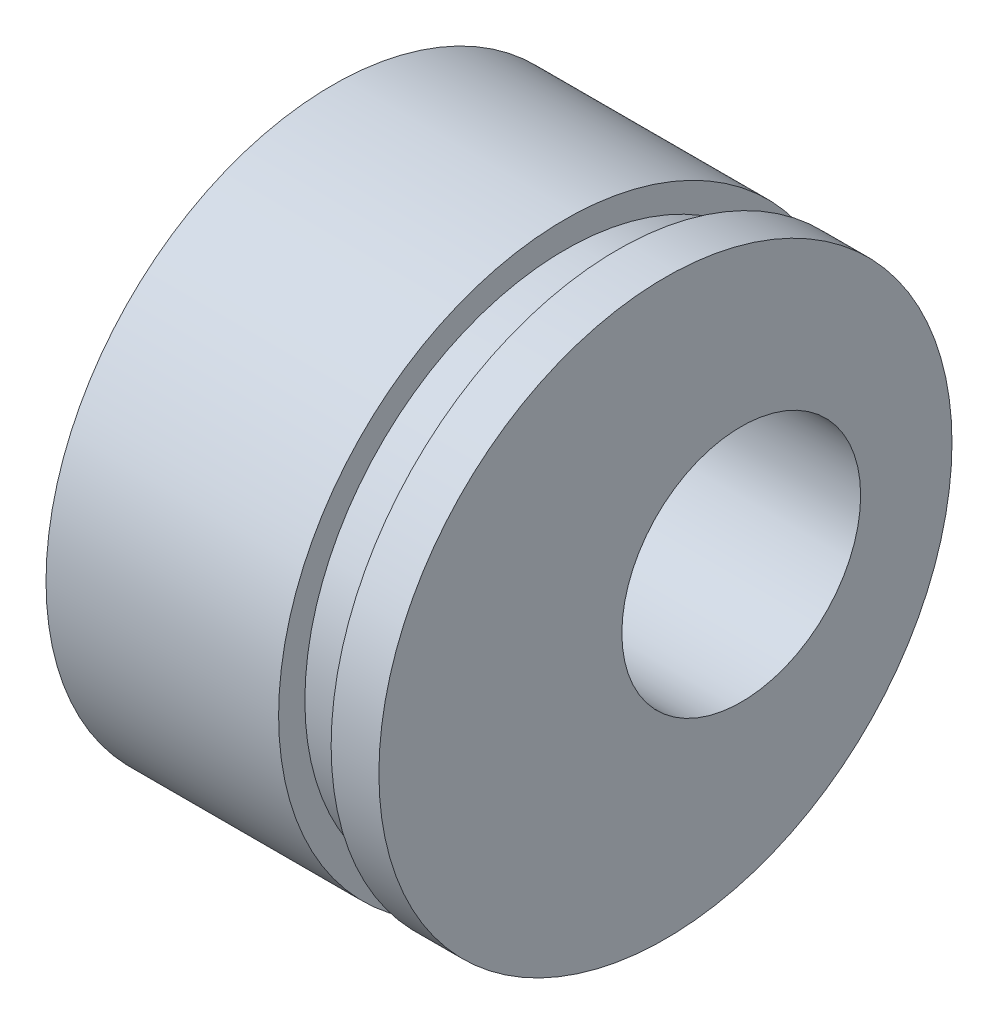
SolidWorks part; units mm, degrees
ref_plane "Front Plane" through (0, 0, 0) normal (0, 0, 1) x (1, 0, 0)
ref_plane "Top Plane" through (0, 0, 0) normal (0, 1, 0) x (1, 0, 0)
ref_plane "Right Plane" through (0, 0, 0) normal (1, 0, 0) x (0, 0, -1)
sketch "Sketch2" plane through (0, 0, 0) normal (0, 0, 1) x (1, 0, 0)
  line L0 (0, 0) -> (58.591, 0) construction
  line L2 (0, 0) -> (18.4, 0)
  line L3 (0, 0) -> (0, 2.5)
  line L4 (0, 2.5) -> (18.4, 2.5)
  line L5 (18.4, 0) -> (18.4, 2.5)
  line L6 (6.0094, 2.5) -> (6.0094, 6)
  line L11 (6.0094, 6) -> (9.9794, 6)
  line L16 (12.9794, 6) -> (12.9794, 3)
  line L17 (12.9794, 3) -> (13.6398, 3)
  line L18 (13.6398, 3) -> (13.6398, 2.5)
  line L19 (13.6398, 2.5) -> (6.0094, 2.5)
  line L22 (13.6398, 2.5) -> (16.1198, 2.5)
  line L23 (13.6398, 2.5) -> (13.6398, 4)
  line L24 (13.6398, 4) -> (16.1198, 4)
  line L25 (16.1198, 2.5) -> (16.1198, 4)
  line L27 (6.0094, 6) -> (9.9794, 6)
  line L28 (6.0094, 6) -> (6.0094, 9)
  line L29 (6.0094, 9) -> (9.9794, 9)
  line L30 (9.9794, 6) -> (9.9794, 9)
  line L31 (6.0094, 9) -> (6.0094, 8.25)
  line L32 (6.0094, 8.25) -> (5.0094, 8.25)
  line L33 (8.6609, 22.001) -> (8.6609, 12.476) construction
  line L34 (5.0094, 12.476) -> (12.3124, 12.476)
  line L35 (9.9794, 9) -> (12.3124, 9)
  line L36 (5.0094, 7.9375) -> (1.8344, 7.9375)
  line L37 (5.0094, 8.25) -> (5.0094, 12.476)
  line L38 (5.0094, 7.9375) -> (5.0094, 13.9365)
  line L39 (5.0094, 13.9365) -> (1.8344, 13.9365)
  line L40 (1.8344, 7.9375) -> (1.8344, 13.9365)
  line L41 (5.0094, 22.001) -> (12.3124, 22.001)
  line L42 (5.0094, 22.001) -> (5.0094, 30.1625)
  line L43 (5.0094, 30.1625) -> (12.3124, 30.1625)
  line L44 (12.3124, 22.001) -> (12.3124, 30.1625)
  line L49 (16.6398, 22.001) -> (16.6398, 7.5)
  line L51 (23.0198, 7.5) -> (23.0198, 6.5)
  line L54 (16.1198, 4) -> (13.6398, 4)
  line L56 (18.0398, 7.5) -> (23.0198, 7.5)
  line L57 (13.3124, 22.001) -> (16.6398, 22.001)
  line L58 (16.1198, 3.5) -> (20.0198, 3.5)
  line L59 (29.9098, 14) -> (26.9098, 11)
  line L60 (4.0094, 31.75) -> (18.0398, 31.75)
  line L61 (18.0398, 7.5) -> (23.0198, 7.5)
  line L62 (18.0398, 7.5) -> (18.0398, 12)
  line L63 (18.0398, 12) -> (23.0198, 12)
  line L64 (23.0198, 7.5) -> (23.0198, 12)
  line L65 (18.0398, 31.75) -> (18.0398, 12)
  line L66 (23.0198, 11) -> (26.9098, 11)
  line L67 (34.8098, 23) -> (31.3098, 19.5)
  line L68 (35.8098, 31) -> (38.7998, 33.99)
  line L69 (29.9098, 14) -> (29.9098, 15)
  line L70 (29.9098, 15) -> (22.9398, 15)
  line L71 (22.9398, 15) -> (21.0398, 15)
  line L72 (18.0398, 7.5) -> (16.6398, 7.5)
  line L73 (21.0398, 15) -> (21.0398, 43)
  line L74 (19.5798, 40) -> (9.6198, 40)
  line L75 (9.6198, 40) -> (4.0094, 40)
  line L76 (21.0398, 43) -> (19.5798, 43)
  line L77 (22.9398, 15) -> (29.9098, 15)
  line L78 (22.9398, 15) -> (22.9398, 21)
  line L79 (22.9398, 21) -> (29.9098, 21)
  line L80 (29.9098, 15) -> (29.9098, 21)
  line L81 (9.6198, 40) -> (19.5798, 40)
  line L82 (9.6198, 40) -> (9.6198, 50)
  line L83 (9.6198, 50) -> (19.5798, 50)
  line L84 (19.5798, 40) -> (19.5798, 50)
  line L85 (4.0094, 40) -> (4.0094, 31.75)
  line L86 (12.9794, 3) -> (12.9794, 2.5)
  line L87 (31.3098, 19.5) -> (29.9098, 19.5)
  line L88 (21.4694, 63.5) -> (21.4694, 51.308)
  line L89 (21.4694, 63.5) -> (25.9398, 63.5)
  line L90 (25.9398, 63.5) -> (25.9398, 25)
  line L91 (27.8398, 25) -> (25.9398, 25)
  line L92 (9.6198, 48) -> (8.1598, 48)
  line L93 (8.1598, 48) -> (8.1598, 53.476)
  line L94 (8.1598, 53.476) -> (19.5798, 53.476)
  line L95 (19.5798, 53.476) -> (19.5798, 50)
  line L96 (13.8698, 63.001) -> (13.8698, 53.476) construction
  line L97 (8.1598, 63.001) -> (19.5798, 63.001)
  line L98 (8.1598, 63.001) -> (8.1598, 68.2625)
  line L99 (8.1598, 68.2625) -> (19.5798, 68.2625)
  line L100 (19.5798, 63.001) -> (19.5798, 68.2625)
  line L101 (12.9794, 6) -> (11.9794, 6)
  line L102 (8.1598, 44.825) -> (4.9848, 44.825)
  line L103 (8.1598, 44.825) -> (8.1598, 54.9365)
  line L104 (8.1598, 54.9365) -> (4.9848, 54.9365)
  line L106 (9.9794, 6) -> (10.8794, 6)
  line L107 (27.8398, 25) -> (34.8098, 25)
  line L108 (34.8098, 25) -> (34.8098, 23)
  line L109 (0, 0) -> (-2, 0)
  line L110 (0, 0) -> (0, 11)
  line L111 (27.8398, 25) -> (34.8098, 25)
  line L112 (27.8398, 25) -> (27.8398, 32.5)
  line L113 (27.8398, 32.5) -> (34.8098, 32.5)
  line L114 (34.8098, 25) -> (34.8098, 32.5)
  line L115 (35.8098, 31) -> (34.8098, 31)
  line L116 (27.8398, 32.5) -> (27.8398, 64.5)
  line L117 (20.5373, 74.025) -> (6.2023, 74.025)
  line L118 (6.2023, 74.025) -> (6.2023, 76.2)
  line L119 (38.7998, 47.29) -> (30.8398, 55.25)
  line L120 (0, 11) -> (-2, 11)
  line L121 (38.7998, 43.815) -> (30.8623, 43.815)
  line L123 (-4.8152, 69.85) -> (1.5348, 76.2)
  line L124 (38.7998, 47.29) -> (38.7998, 33.99)
  line L125 (-2, 0) -> (-2, 11)
  line L126 (38.7998, 37.465) -> (30.8623, 37.465)
  line L127 (30.8623, 43.815) -> (30.8623, 37.465)
  line L128 (6.0094, 2.5) -> (6.0094, 0)
  line L129 (-0.0152, 63.5) -> (-0.0152, 30)
  line L132 (4.9848, 63.5) -> (-0.0152, 63.5)
  line L136 (-1.8152, 30) -> (-11.7752, 30)
  line L138 (-13.7752, 25.4) -> (-2, 25.4)
  line L139 (-2, 25.4) -> (-2, 11.5)
  line L140 (27.8398, 64.5) -> (20.5373, 64.5)
  line L141 (-1.8152, 30) -> (-11.7752, 30)
  line L142 (-1.8152, 30) -> (-1.8152, 39)
  line L143 (-1.8152, 39) -> (-11.7752, 39)
  line L144 (-11.7752, 30) -> (-11.7752, 39)
  line L145 (20.5373, 64.5) -> (20.5373, 74.025)
  line L146 (-12.7752, 37) -> (-12.7752, 47.29)
  line L147 (-12.7752, 37) -> (-11.7752, 37)
  line L148 (30.8398, 55.25) -> (30.8398, 76.2)
  line L149 (11.9794, 6) -> (11.9794, 5.45)
  line L154 (-2, 11.5) -> (0.5, 11.5)
  line L155 (4.9848, 60.6197) -> (24.0348, 60.6197)
  line L160 (4.9848, 60.6197) -> (4.9848, 55.8572)
  line L161 (4.9848, 55.8572) -> (24.0348, 55.8572)
  line L166 (24.0348, 60.6197) -> (24.0348, 55.8572)
  line L167 (4.9848, 60.6197) -> (24.0348, 55.8572) construction
  line L172 (4.9848, 55.8572) -> (24.0348, 60.6197) construction
  line L173 (24.0348, 62.2072) -> (25.9398, 62.2072)
  line L174 (11.9794, 5.45) -> (10.8794, 5.45)
  line L175 (10.8794, 6) -> (10.8794, 5.45)
  line L176 (24.0348, 62.2072) -> (24.0348, 54.2697)
  line L177 (24.0348, 54.2697) -> (25.9398, 54.2697)
  line L178 (25.9398, 62.2072) -> (25.9398, 54.2697)
  line L179 (24.0348, 62.2072) -> (25.9398, 54.2697) construction
  line L180 (24.0348, 54.2697) -> (25.9398, 62.2072) construction
  line L181 (3, 19.6197) -> (15.7, 19.6197)
  line L182 (3, 19.6197) -> (3, 14.8572)
  line L183 (3, 14.8572) -> (15.7, 14.8572)
  line L184 (15.7, 19.6197) -> (15.7, 14.8572)
  line L185 (3, 19.6197) -> (15.7, 14.8572) construction
  line L186 (3, 14.8572) -> (15.7, 19.6197) construction
  line L187 (15.7, 21.2072) -> (16.6398, 21.2072)
  line L188 (15.7, 21.2072) -> (15.7, 13.2697)
  line L189 (15.7, 13.2697) -> (16.6398, 13.2697)
  line L190 (16.6398, 21.2072) -> (16.6398, 13.2697)
  line L191 (15.7, 21.2072) -> (16.6398, 13.2697) construction
  line L192 (15.7, 13.2697) -> (16.6398, 21.2072) construction
  line L193 (0.5, 11.5) -> (0.5, 6.9375)
  line L194 (0.5, 6.9375) -> (1.8344, 6.9375)
  line L195 (23.0198, 6.5) -> (20.0198, 3.5)
  line L196 (4.9848, 63.5) -> (4.9848, 54.9365)
  line L197 (3, 43.825) -> (4.9848, 43.825)
  line L198 (1.8344, 6.9375) -> (1.8344, 7.9375)
  line L199 (6.0094, 0) -> (12.9794, 0)
  line L200 (12.9794, 0) -> (12.9794, 2.5)
  line L201 (18.0398, 31.75) -> (18.0398, 35.875)
  line L202 (18.0398, 35.875) -> (21.0398, 35.875)
  line L203 (30.8398, 76.2) -> (6.2023, 76.2)
  line L204 (2.7573, 69.85) -> (7.2023, 69.85) construction
  line L205 (7.2023, 67.4688) -> (26.2523, 67.4688)
  line L206 (7.2023, 74.025) -> (7.2023, 64.5)
  line L207 (7.2023, 64.5) -> (-1.8152, 64.5)
  line L208 (-1.8152, 64.5) -> (-1.8152, 39)
  line L209 (-12.7752, 47.29) -> (-4.8152, 55.25)
  line L210 (-4.8152, 55.25) -> (-4.8152, 69.85)
  line L211 (7.2023, 67.4688) -> (7.2023, 72.2312)
  line L212 (7.2023, 72.2312) -> (26.2523, 72.2313)
  line L213 (26.2523, 67.4688) -> (26.2523, 72.2313)
  line L214 (26.2523, 73.8187) -> (30.8398, 73.8187)
  line L215 (26.2523, 73.8187) -> (26.2523, 65.8813)
  line L216 (26.2523, 65.8813) -> (30.8398, 65.8813)
  line L217 (30.8398, 73.8187) -> (30.8398, 65.8813)
  line L218 (2.7573, 72.2313) -> (24.9823, 72.2313)
  line L219 (2.7573, 72.2313) -> (2.7573, 67.4687)
  line L220 (2.7573, 67.4687) -> (24.9823, 67.4687)
  line L221 (24.9823, 72.2313) -> (24.9823, 67.4687)
  line L222 (24.9823, 69.85) -> (20.5373, 69.85) construction
  line L223 (21.4694, 51.308) -> (22.9398, 51.308)
  line L224 (22.9398, 51.308) -> (22.9398, 21)
  line L225 (13.6398, 4) -> (13.6398, 12.2697)
  line L226 (13.6398, 12.2697) -> (13.3124, 12.2697)
  line L227 (13.3124, 12.2697) -> (13.3124, 22.001)
  line L228 (12.3124, 9) -> (12.3124, 12.476)
  line L229 (-1.8152, 30) -> (-0.0152, 30)
  line L230 (8.1598, 65.6317) -> (2.7573, 65.6317) construction
  line L231 (19.5798, 65.6317) -> (24.9823, 65.6317) construction
  line L232 (1.5348, 76.2) -> (6.2023, 76.2)
  line L233 (-11.7752, 30) -> (-13.7752, 30)
  line L234 (-13.7752, 30) -> (-13.7752, 25.4)
  line L235 (3, 13.9365) -> (3, 43.825)
  line L236 (4.9848, 54.9365) -> (4.9848, 44.825)
  line L237 (4.9848, 43.825) -> (4.9848, 44.825)
  circle A0 centre (26.8898, 25.95) radius 0.95
  circle A1 centre (21.9898, 15.95) radius 0.95
  circle A2 centre (17.3398, 8.2) radius 0.7
  circle A3 centre (10.4294, 6.45) radius 0.45
  circle A4 centre (-0.9152, 30.9) radius 0.9
  point P7 (24.9873, 58.2385)
  point P131 (16.1699, 17.2385)
  point P135 (14.5098, 58.2385)
  point P146 (9.35, 17.2385)
sketch "Sketch3" plane through (0, 0, 0) normal (0, 0, 1) x (1, 0, 0)
  line L0 (12.9794, 3) -> (12.9794, 2.5) construction
  line L1 (11.9794, 6) -> (11.9794, 5.45) construction
  line L2 (12.9794, 6) -> (11.9794, 6) construction
  line L3 (12.9794, 6) -> (12.9794, 3) construction
  line L5 (10.8794, 6) -> (10.8794, 5.45) construction
  line L6 (11.9794, 5.45) -> (10.8794, 5.45) construction
  line L7 (6.0094, 2.5) -> (6.0094, 6) construction
  line L8 (6.0094, 6) -> (9.9794, 6) construction
  line L9 (9.9794, 6) -> (10.8794, 6) construction
  line L10 (12.9794, 3) -> (12.9794, 2.5)
  line L11 (11.9794, 6) -> (11.9794, 5.45)
  line L12 (12.9794, 6) -> (11.9794, 6)
  line L13 (12.9794, 6) -> (12.9794, 3)
  line L15 (10.8794, 6) -> (10.8794, 5.45)
  line L16 (11.9794, 5.45) -> (10.8794, 5.45)
  line L17 (6.0094, 2.5) -> (6.0094, 6)
  line L18 (6.0094, 6) -> (9.9794, 6)
  line L19 (9.9794, 6) -> (10.8794, 6)
  line L20 (6.0094, 2.5) -> (6.0094, 0) construction
  line L21 (0, 0) -> (18.4, 0) construction
  line L22 (12.9794, 0) -> (12.9794, 2.5) construction
  line L23 (6.0094, 2.5) -> (6.0094, 0)
  line L24 (6.0094, 0) -> (12.9794, 0)
  line L25 (12.9794, 0) -> (12.9794, 2.5)
revolve "Revolve1" add sketch "Sketch3" angle 360 about L24
sketch "Sketch4" plane through (0, 0, 0) normal (1, 0, 0) x (0, 0, -1)
  line L0 (0, 0) -> (0, 69.85) construction
  line L1 (0, 0) -> (13.6271, 68.5079) construction
  line L2 (0, 0) -> (0, 58.2385) construction
  line L3 (0, 0) -> (50.436, 29.1192) construction
  line L4 (0, 0) -> (0, 31.75) construction
  line L5 (0, 0) -> (12.1502, 29.3332) construction
  line L6 (0, 0) -> (0, 17.2385) construction
  line L7 (0, 0) -> (14.929, 8.6192) construction
  line L8 (0, 0) -> (0, 58.2385) construction
  line L9 (0, 0) -> (50.436, 29.1192) construction
  line L10 (0, 0) -> (5.9583, 29.9542) construction
  line L11 (0, 0) -> (16.9677, 25.394) construction
  circle A0 centre (0, 0) radius 69.85 construction
  circle A1 centre (0, 0) radius 58.2385 construction
  circle A2 centre (0, 0) radius 31.75 construction
  circle A3 centre (0, 0) radius 17.2385 construction
  circle A4 centre (0, 69.85) radius 3.175
  circle A5 centre (0, 58.2385) radius 4.7625
  circle A6 centre (0, 31.75) radius 3.175
  circle A7 centre (0, 17.2385) radius 4.7625
  circle A8 centre (13.6271, 68.5079) radius 3.175
  circle A9 centre (26.7304, 64.533) radius 3.175
  circle A10 centre (38.8066, 58.0782) radius 3.175
  circle A11 centre (49.3914, 49.3914) radius 3.175
  circle A12 centre (58.0782, 38.8066) radius 3.175
  circle A13 centre (64.533, 26.7304) radius 3.175
  circle A14 centre (68.5079, 13.6271) radius 3.175
  circle A15 centre (69.85, 0) radius 3.175
  circle A16 centre (68.5079, -13.6271) radius 3.175
  circle A17 centre (64.533, -26.7304) radius 3.175
  circle A18 centre (58.0782, -38.8066) radius 3.175
  circle A19 centre (49.3914, -49.3914) radius 3.175
  circle A20 centre (38.8066, -58.0782) radius 3.175
  circle A21 centre (26.7304, -64.533) radius 3.175
  circle A22 centre (13.6271, -68.5079) radius 3.175
  circle A23 centre (0, -69.85) radius 3.175
  circle A24 centre (-13.6271, -68.5079) radius 3.175
  circle A25 centre (-26.7304, -64.533) radius 3.175
  circle A26 centre (-38.8066, -58.0782) radius 3.175
  circle A27 centre (-49.3914, -49.3914) radius 3.175
  circle A28 centre (-58.0782, -38.8066) radius 3.175
  circle A29 centre (-64.533, -26.7304) radius 3.175
  circle A30 centre (-68.5079, -13.6271) radius 3.175
  circle A31 centre (-69.85, 0) radius 3.175
  circle A32 centre (-68.5079, 13.6271) radius 3.175
  circle A33 centre (-64.533, 26.7304) radius 3.175
  circle A34 centre (-58.0782, 38.8066) radius 3.175
  circle A35 centre (-49.3914, 49.3914) radius 3.175
  circle A36 centre (-38.8066, 58.0782) radius 3.175
  circle A37 centre (-26.7304, 64.533) radius 3.175
  circle A38 centre (-13.6271, 68.5079) radius 3.175
  circle A47 centre (50.436, 29.1192) radius 4.7625
  circle A48 centre (50.436, -29.1192) radius 4.7625
  circle A49 centre (0, -58.2385) radius 4.7625
  circle A50 centre (-50.436, -29.1192) radius 4.7625
  circle A51 centre (-50.436, 29.1192) radius 4.7625
  circle A58 centre (12.1502, 29.3332) radius 3.175
  circle A59 centre (22.4506, 22.4506) radius 3.175
  circle A60 centre (29.3332, 12.1502) radius 3.175
  circle A61 centre (31.75, 0) radius 3.175
  circle A62 centre (29.3332, -12.1502) radius 3.175
  circle A63 centre (22.4506, -22.4506) radius 3.175
  circle A64 centre (12.1502, -29.3332) radius 3.175
  circle A65 centre (0, -31.75) radius 3.175
  circle A66 centre (-12.1502, -29.3332) radius 3.175
  circle A67 centre (-22.4506, -22.4506) radius 3.175
  circle A68 centre (-29.3332, -12.1502) radius 3.175
  circle A69 centre (-31.75, 0) radius 3.175
  circle A70 centre (-29.3332, 12.1502) radius 3.175
  circle A71 centre (-22.4506, 22.4506) radius 3.175
  circle A72 centre (14.929, 8.6192) radius 4.7625
  circle A73 centre (14.929, -8.6192) radius 4.7625
  circle A74 centre (0, -17.2385) radius 4.7625
  circle A75 centre (-14.929, -8.6192) radius 4.7625
  circle A76 centre (-14.929, 8.6192) radius 4.7625
  circle A77 centre (0, 0) radius 50
  circle A78 centre (0, 0) radius 9
  circle A79 centre (-12.1502, 29.3332) radius 3.175
  circle A80 centre (0, 0) radius 76.2
  circle A81 centre (0, 0) radius 74.025
  circle A82 centre (0, 69.85) radius 3.9687
  circle A83 centre (49.3914, 49.3914) radius 3.9687
  circle A84 centre (69.85, 0) radius 3.9688
  circle A85 centre (49.3914, -49.3914) radius 3.9687
  circle A86 centre (0, -69.85) radius 3.9687
  circle A87 centre (-49.3914, -49.3914) radius 3.9687
  circle A88 centre (-69.85, 0) radius 3.9688
  circle A89 centre (-49.3914, 49.3914) radius 3.9687
  circle A90 centre (0, 69.85) radius 2.3812
  circle A91 centre (13.6271, 68.5079) radius 2.3812
  circle A92 centre (26.7304, 64.533) radius 2.3813
  circle A93 centre (38.8066, 58.0782) radius 2.3812
  circle A94 centre (49.3914, 49.3914) radius 2.3812
  circle A95 centre (58.0782, 38.8066) radius 2.3812
  circle A96 centre (64.533, 26.7304) radius 2.3813
  circle A97 centre (68.5079, 13.6271) radius 2.3813
  circle A98 centre (69.85, 0) radius 2.3813
  circle A99 centre (68.5079, -13.6271) radius 2.3813
  circle A100 centre (64.533, -26.7304) radius 2.3813
  circle A101 centre (58.0782, -38.8066) radius 2.3812
  circle A102 centre (49.3914, -49.3914) radius 2.3812
  circle A103 centre (38.8066, -58.0782) radius 2.3812
  circle A104 centre (26.7304, -64.533) radius 2.3813
  circle A105 centre (13.6271, -68.5079) radius 2.3812
  circle A106 centre (0, -69.85) radius 2.3812
  circle A107 centre (-13.6271, -68.5079) radius 2.3812
  circle A108 centre (-26.7304, -64.533) radius 2.3813
  circle A109 centre (-38.8066, -58.0782) radius 2.3812
  circle A110 centre (-49.3914, -49.3914) radius 2.3812
  circle A111 centre (-58.0782, -38.8066) radius 2.3812
  circle A112 centre (-64.533, -26.7304) radius 2.3812
  arc A113 (3.0399, 30.8338) -> (8.9911, 29.65) centre (5.9583, 29.9542) cw
  arc A114 (14.6081, 27.3234) -> (19.6532, 23.9523) centre (16.9677, 25.394) cw
  arc A115 (23.9523, 19.6532) -> (27.3234, 14.6081) centre (25.394, 16.9677) cw
  arc A116 (29.65, 8.9911) -> (30.8338, 3.0399) centre (29.9542, 5.9583) cw
  arc A117 (30.8338, -3.0399) -> (29.65, -8.9911) centre (29.9542, -5.9583) cw
  arc A118 (27.3234, -14.6081) -> (23.9523, -19.6532) centre (25.394, -16.9677) cw
  arc A119 (19.6532, -23.9523) -> (14.6081, -27.3234) centre (16.9677, -25.394) cw
  arc A120 (8.9911, -29.65) -> (3.0399, -30.8338) centre (5.9583, -29.9542) cw
  arc A121 (-3.0399, -30.8338) -> (-8.9911, -29.65) centre (-5.9583, -29.9542) cw
  arc A122 (-14.6081, -27.3234) -> (-19.6532, -23.9523) centre (-16.9677, -25.394) cw
  arc A123 (-23.9523, -19.6532) -> (-27.3234, -14.6081) centre (-25.394, -16.9677) cw
  arc A124 (-29.65, -8.9911) -> (-30.8338, -3.0399) centre (-29.9542, -5.9583) cw
  arc A125 (-30.8338, 3.0399) -> (-29.65, 8.9911) centre (-29.9542, 5.9583) cw
  arc A126 (-27.3234, 14.6081) -> (-23.9523, 19.6532) centre (-25.394, 16.9677) cw
  arc A127 (-19.6532, 23.9523) -> (-14.6081, 27.3234) centre (-16.9677, 25.394) cw
  arc A128 (-8.9911, 29.65) -> (-3.0399, 30.8338) centre (-5.9583, 29.9542) cw
  arc A129 (26.9875, 0) -> (26.9932, 0.1932) centre (30.2705, 0) cw
  arc A130 (65.0988, 0.2771) -> (65.0875, 0) centre (68.4964, 0) ccw
  circle A131 centre (1.5875, 0) radius 40
  circle A132 centre (1.5875, 0) radius 2.5
  circle A133 centre (1.5875, 0) radius 3
  circle A134 centre (1.5875, 0) radius 43
  circle A135 centre (-68.5079, -13.6271) radius 2.3813
  circle A136 centre (-69.85, 0) radius 2.3813
  circle A137 centre (-68.5079, 13.6271) radius 2.3813
  circle A138 centre (-64.533, 26.7304) radius 2.3812
  circle A139 centre (-58.0782, 38.8066) radius 2.3812
  circle A140 centre (-49.3914, 49.3914) radius 2.3812
  circle A141 centre (-38.8066, 58.0782) radius 2.3812
  circle A142 centre (-26.7304, 64.533) radius 2.3813
  circle A143 centre (-13.6271, 68.5079) radius 2.3812
  circle A144 centre (0, 58.2385) radius 2.3812
  circle A145 centre (0, 58.2385) radius 3.9688
  circle A146 centre (50.436, 29.1192) radius 3.9688
  circle A147 centre (50.436, 29.1192) radius 2.3813
  circle A148 centre (50.436, -29.1192) radius 3.9687
  circle A149 centre (50.436, -29.1192) radius 2.3812
  circle A150 centre (0, -58.2385) radius 3.9687
  circle A151 centre (0, -58.2385) radius 2.3812
  circle A152 centre (-50.436, -29.1192) radius 3.9687
  circle A153 centre (-50.436, -29.1192) radius 2.3812
  circle A154 centre (-50.436, 29.1192) radius 3.9687
  circle A155 centre (-50.436, 29.1192) radius 2.3812
  spline S1 degree 4 poles (26.9875, 0) (26.9875, -0.0248) (26.9882, -0.0743) (26.9912, -0.1613) (26.9992, -0.2849) (27.0142, -0.4323) (27.0403, -0.5994) (27.0821, -0.7965) (27.1455, -1.0177) (27.2241, -1.2336) (27.3173, -1.4437) (27.4329, -1.6623) (27.5739, -1.8864) (27.7427, -2.1125) (27.9417, -2.3365) (28.1305, -2.5184) (28.3007, -2.6647) (28.4457, -2.7828) (28.5617, -2.8775) (28.6745, -2.9758) (28.7813, -3.0807) (28.9057, -3.2206) (29.0482, -3.4108) (29.197, -3.6576) (29.3758, -4.0447) (29.5291, -4.5502) (29.6152, -5.1612) (29.5933, -5.8758) (29.4507, -6.5869) (29.186, -7.2733) (28.8461, -7.831) (28.4818, -8.2549) (28.1375, -8.5536) (27.8792, -8.7284) (27.6484, -8.8496) (27.4154, -8.9438) (27.2144, -9.0029) (27.0118, -9.0554) (26.7709, -9.1263) (26.5334, -9.2082) (26.2634, -9.3231) (25.9685, -9.4827) (25.5538, -9.7623) (25.0678, -10.2216) (24.6281, -10.8948) (24.3613, -11.7878) (24.3459, -12.6097) (24.4764, -13.2366) (24.6525, -13.7006) (24.8058, -14.0202) (24.9382, -14.271) (25.0503, -14.5321) (25.1258, -14.8064) (25.1736, -15.0995) (25.1911, -15.4094) (25.1742, -15.8163) (25.0891, -16.3148) (24.907, -16.8764) (24.5182, -17.6315) (23.9757, -18.2942) (23.3695, -18.7764) (22.7564, -19.084) (22.3641, -19.2199) (22.0554, -19.2923) (21.7533, -19.3289) (21.4612, -19.3296) (21.1723, -19.2896) (20.8852, -19.2417) (20.5956, -19.2104) (20.3043, -19.1994) (19.8669, -19.2177) (19.2899, -19.3231) (18.5833, -19.6092) (17.8444, -20.1834) (17.3807, -20.828) (17.1316, -21.424) (17.0182, -21.8879) (16.9714, -22.1971) (16.9537, -22.4701) (16.9533, -22.7044) (16.9619, -22.9384) (16.9737, -23.1333) (16.977, -23.3286) (16.9594, -23.5624) (16.9177, -23.8101) (16.834, -24.1055) (16.6578, -24.5276) (16.3623, -25.0151) (15.9278, -25.5198) (15.3432, -25.99) (14.6957, -26.3472) (14.0068, -26.5857) (13.3856, -26.6851) (12.847, -26.6849) (12.4166, -26.6224) (12.1324, -26.5468) (11.9058, -26.4598) (11.7342, -26.3753) (11.6017, -26.2989) (11.4727, -26.2169) (11.3444, -26.1337) (11.1825, -26.0322) (10.9836, -25.9179) (10.7435, -25.7991) (10.4587, -25.6867) (10.0106, -25.5536) (9.3843, -25.468) (8.599, -25.5363) (7.7243, -25.8773) (7.1093, -26.3459) (6.716, -26.8042) (6.4745, -27.1841) (6.3352, -27.4489) (6.215, -27.7227) (6.1113, -28.0028) (5.9959, -28.2789) (5.841, -28.5357) (5.6522, -28.7792) (5.4316, -29.007) (5.1188, -29.2711) (4.6965, -29.5439) (4.1624, -29.7882) (3.5487, -29.9564) (2.9521, -30.0296) (2.386, -30.0225) (1.8595, -29.949) (1.3409, -29.8055) (0.9058, -29.6147) (0.5544, -29.4004) (0.2828, -29.1832) (0.0847, -28.9875) (-0.0865, -28.768) (-0.2353, -28.5332) (-0.3904, -28.3016) (-0.5598, -28.0786) (-0.792, -27.8146) (-1.1036, -27.5274) (-1.5105, -27.2448) (-2.0688, -26.9834) (-2.7167, -26.8202) (-3.459, -26.7949) (-4.1529, -26.9407) (-4.7224, -27.1899) (-5.1296, -27.455) (-5.3866, -27.661) (-5.5925, -27.8507) (-5.7558, -28.014) (-5.9199, -28.1766) (-6.0977, -28.3246) (-6.3382, -28.4851) (-6.6906, -28.6628) (-7.1669, -28.8182) (-7.7668, -28.9076) (-8.4201, -28.8957) (-9.0747, -28.7804) (-9.7144, -28.5614) (-10.3217, -28.2381) (-10.8061, -27.8636) (-11.1671, -27.4837) (-11.4143, -27.1402) (-11.5734, -26.859) (-11.6946, -26.573) (-11.7735, -26.2857) (-11.8173, -25.9915) (-11.8668, -25.6988) (-11.9353, -25.4093) (-12.0257, -25.1261) (-12.198, -24.7091) (-12.5089, -24.187) (-13.0379, -23.6191) (-13.8448, -23.1355) (-14.6072, -22.9365) (-15.2369, -22.9149) (-15.701, -22.9694) (-16.0024, -23.0316) (-16.2609, -23.107) (-16.4782, -23.1841) (-16.6576, -23.2529) (-16.8015, -23.307) (-16.9839, -23.3672) (-17.2087, -23.4203) (-17.4853, -23.4534) (-17.811, -23.4543) (-18.2291, -23.4104) (-18.7305, -23.2885) (-19.2884, -23.06) (-19.8603, -22.7052) (-20.3581, -22.2764) (-20.7758, -21.7899) (-21.1086, -21.2598) (-21.3336, -20.7318) (-21.4619, -20.2263) (-21.5006, -19.8113) (-21.4889, -19.4989) (-21.4468, -19.2424) (-21.3965, -19.0408) (-21.34, -18.8332) (-21.2878, -18.6168) (-21.2341, -18.3322) (-21.1962, -17.9773) (-21.1985, -17.5604) (-21.2781, -17.0173) (-21.4721, -16.4256) (-21.838, -15.7861) (-22.3482, -15.2578) (-22.8946, -14.8957) (-23.3828, -14.6878) (-23.7368, -14.5834) (-24.0536, -14.5215) (-24.3285, -14.4876) (-24.6045, -14.47) (-24.8811, -14.458) (-25.1556, -14.4184) (-25.4228, -14.3439) (-25.6932, -14.2375) (-26.1109, -14.0218) (-26.5677, -13.6822) (-27.0258, -13.1981) (-27.4314, -12.5682) (-27.7017, -11.9578) (-27.8746, -11.3112) (-27.9332, -10.727) (-27.9111, -10.2247) (-27.8415, -9.8214) (-27.7568, -9.5159) (-27.6427, -9.2298) (-27.5004, -8.9659) (-27.3212, -8.7261) (-27.1301, -8.4966) (-26.9071, -8.1967) (-26.6417, -7.7583) (-26.3997, -7.1508) (-26.2841, -6.3875) (-26.3642, -5.5798) (-26.6019, -4.9055) (-26.9193, -4.3761) (-27.2736, -3.9636) (-27.583, -3.6904) (-27.8719, -3.4871) (-28.1186, -3.3407) (-28.3135, -3.2371) (-28.5043, -3.1411) (-28.6854, -3.0419) (-28.9002, -2.8984) (-29.1355, -2.6958) (-29.4123, -2.3882) (-29.6958, -1.9552) (-29.932, -1.437) (-30.0985, -0.839) (-30.1779, -0.2025) (-30.1603, 0.4599) (-30.0348, 1.1323) (-29.8199, 1.711) (-29.5617, 2.1719) (-29.3035, 2.5118) (-29.0784, 2.748) (-28.8655, 2.924) (-28.6761, 3.0468) (-28.5112, 3.1367) (-28.3775, 3.205) (-28.2106, 3.2911) (-28.0136, 3.4005) (-27.7912, 3.5413) (-27.5508, 3.7219) (-27.2011, 4.0343) (-26.7941, 4.5285) (-26.4419, 5.234) (-26.2777, 6.1494) (-26.351, 6.9081) (-26.5268, 7.4739) (-26.7218, 7.8823) (-26.8619, 8.1196) (-26.9953, 8.3144) (-27.1373, 8.5028) (-27.2613, 8.6553) (-27.3845, 8.8088) (-27.518, 9.0035) (-27.6324, 9.2103) (-27.7412, 9.4693) (-27.8326, 9.7814) (-27.9074, 10.1885) (-27.9345, 10.6913) (-27.8808, 11.2771) (-27.6878, 12.0229) (-27.3166, 12.8111) (-26.8405, 13.4278) (-26.3243, 13.8718) (-25.9118, 14.1263) (-25.6503, 14.2566) (-25.3769, 14.3596) (-25.0933, 14.4318) (-24.8027, 14.4634) (-24.5112, 14.4738) (-24.1629, 14.5033) (-23.7608, 14.5717) (-23.1887, 14.7443) (-22.5511, 15.0901) (-21.962, 15.6231) (-21.544, 16.2749) (-21.3217, 16.857) (-21.2175, 17.3851) (-21.1902, 17.8397) (-21.2185, 18.2374) (-21.2771, 18.5739) (-21.3443, 18.8506) (-21.405, 19.0706) (-21.4579, 19.2928) (-21.4883, 19.5194) (-21.4981, 19.805) (-21.4664, 20.1907) (-21.3565, 20.6672) (-21.1331, 21.2135) (-20.8025, 21.7541) (-20.3882, 22.2461) (-19.8974, 22.677) (-19.3379, 23.033) (-18.7964, 23.2649) (-18.309, 23.3941) (-17.8981, 23.4483) (-17.5726, 23.4572) (-17.2924, 23.4331) (-17.0602, 23.3874) (-16.8337, 23.3199) (-16.6495, 23.2499) (-16.4659, 23.1791) (-16.2424, 23.1025) (-16.0156, 23.0362) (-15.7461, 22.9768) (-15.2967, 22.9185) (-14.7035, 22.9278) (-13.9592, 23.0948) (-13.1407, 23.5365) (-12.5805, 24.0908) (-12.2382, 24.6309) (-12.0505, 25.0599) (-11.9538, 25.3442) (-11.8892, 25.5989) (-11.8463, 25.8198) (-11.8162, 26.0048) (-11.7926, 26.153) (-11.7577, 26.3372) (-11.6989, 26.5548) (-11.5969, 26.8111) (-11.4414, 27.0975) (-11.1977, 27.4473) (-10.8392, 27.8343) (-10.3554, 28.2166) (-9.7549, 28.5431) (-9.1303, 28.7642) (-8.5, 28.8851) (-7.879, 28.911) (-7.3126, 28.8458) (-6.8128, 28.7091) (-6.4345, 28.54) (-6.1692, 28.378) (-5.9665, 28.2173) (-5.8163, 28.0752) (-5.6659, 27.9232) (-5.5067, 27.7699) (-5.2907, 27.5806) (-5.0072, 27.369) (-4.6509, 27.1597) (-4.148, 26.9513) (-3.5452, 26.8146) (-2.8302, 26.7991) (-2.0381, 26.9749) (-1.3495, 27.3225) (-0.8483, 27.741) (-0.5146, 28.1291) (-0.2991, 28.4338) (-0.1401, 28.6862) (0.0331, 28.93) (0.2405, 29.146) (0.4774, 29.3422) (0.7418, 29.5165) (1.1036, 29.7066) (1.5741, 29.882) (2.1471, 30.006) (2.8151, 30.041) (3.4791, 29.9721) (4.2039, 29.7804) (4.8064, 29.4933) (5.2708, 29.1628) (5.6049, 28.8311) (5.7894, 28.6062) (5.9424, 28.3744) (6.0642, 28.1249) (6.161, 27.8653) (6.2635, 27.608) (6.3813, 27.357) (6.5388, 27.0748) (6.7484, 26.7704) (7.0986, 26.3707) (7.6135, 25.9641) (8.2747, 25.644) (8.9962, 25.4959) (9.6181, 25.496) (10.1582, 25.5894) (10.5546, 25.7168) (10.8796, 25.8629) (11.1331, 26.0022) (11.3224, 26.1188) (11.5021, 26.2366) (11.6784, 26.3463) (11.9094, 26.4649) (12.2028, 26.5718) (12.6092, 26.6624) (13.1291, 26.6958) (13.7, 26.6444) (14.3062, 26.4914) (14.8974, 26.2443) (15.459, 25.9029) (15.9732, 25.4681) (16.3631, 25.0071) (16.6337, 24.567) (16.8044, 24.1822) (16.9036, 23.8716) (16.9571, 23.5978) (16.9755, 23.3672) (16.9741, 23.1748) (16.9669, 23.0211) (16.9571, 22.8289) (16.9512, 22.5982) (16.9599, 22.3287) (16.9946, 22.0224) (17.0874, 21.5638) (17.3043, 20.9714) (17.7315, 20.3087) (18.4426, 19.693) (19.1468, 19.3677) (19.739, 19.2351) (20.1882, 19.2012) (20.4852, 19.2034) (20.7812, 19.2282) (21.0745, 19.2719) (21.3675, 19.3208) (21.6648, 19.3336) (21.9737, 19.306) (22.2899, 19.241) (22.6922, 19.1116) (23.1641, 18.8854) (23.669, 18.5404) (24.1634, 18.0628) (24.569, 17.5219) (24.8807, 16.9345) (25.0937, 16.316) (25.184, 15.7743) (25.1924, 15.3317) (25.1581, 14.9969) (25.1154, 14.7695) (25.0522, 14.5468) (24.9658, 14.3321) (24.8616, 14.1257) (24.7568, 13.9198) (24.6402, 13.6649) (24.524, 13.3562) (24.3985, 12.886) (24.3389, 12.2663) (24.4166, 11.5605) (24.6979, 10.7931) (25.0952, 10.2042) (25.5426, 9.7706) (25.9551, 9.4883) (26.2689, 9.3208) (26.5627, 9.1971) (26.83, 9.1062) (27.1019, 9.0315) (27.3749, 8.9598) (27.6385, 8.8574) (27.887, 8.7225) (28.1969, 8.5098) (28.5449, 8.1936) (28.9002, 7.7549) (29.2229, 7.1817) (29.4529, 6.562) (29.5858, 5.9108) (29.6165, 5.2432) (29.5485, 4.659) (29.4188, 4.1725) (29.2636, 3.7931) (29.1144, 3.5129) (28.9404, 3.2582) (28.7432, 3.0317) (28.5155, 2.8371) (28.281, 2.6515) (28.0578, 2.4519) (27.8492, 2.2371) (27.6347, 1.9761) (27.4574, 1.7102) (27.3152, 1.4444) (27.2047, 1.1845) (27.1307, 0.9703) (27.0789, 0.7793) (27.0441, 0.6164) (27.021, 0.472) (27.0061, 0.351) (26.9981, 0.2662) (26.9946, 0.2176) (26.9932, 0.1932) knots 0.06864 0.06864 0.06864 0.06864 0.06864 0.069106 0.069571 0.070037 0.070502 0.071433 0.072364 0.073295 0.074226 0.075157 0.076088 0.077301 0.078514 0.079727 0.08094 0.081547 0.082153 0.08276 0.083366 0.083973 0.084579 0.085792 0.087214 0.088636 0.091479 0.094323 0.097166 0.100174 0.103182 0.10619 0.107694 0.109198 0.110555 0.111234 0.111912 0.113269 0.113948 0.114626 0.115983 0.11734 0.118697 0.120055 0.12408 0.128106 0.131537 0.134967 0.137266 0.138415 0.139565 0.140714 0.141863 0.143013 0.144162 0.145524 0.146885 0.149608 0.152331 0.155054 0.160594 0.163364 0.164749 0.166134 0.167314 0.168495 0.169675 0.170855 0.172035 0.173215 0.174395 0.175575 0.179125 0.182676 0.186612 0.190548 0.191813 0.193079 0.194345 0.195611 0.196244 0.196877 0.198142 0.198775 0.199408 0.200674 0.202207 0.203741 0.206808 0.209874 0.212941 0.21584 0.218738 0.221637 0.223086 0.224535 0.225775 0.226394 0.227014 0.227634 0.228253 0.228873 0.229493 0.230732 0.231971 0.233211 0.23445 0.238303 0.242155 0.245814 0.249472 0.250683 0.251894 0.253105 0.254316 0.255527 0.256738 0.257949 0.25916 0.260514 0.261868 0.264577 0.267285 0.269993 0.272142 0.27429 0.276439 0.278588 0.280839 0.281965 0.283091 0.284217 0.285343 0.286469 0.287595 0.288737 0.289879 0.292163 0.294447 0.296732 0.299827 0.302922 0.306383 0.308113 0.309844 0.31078 0.311716 0.312652 0.313588 0.314524 0.31546 0.317332 0.319969 0.322606 0.325244 0.327881 0.330703 0.333524 0.336346 0.337757 0.339168 0.340372 0.341576 0.34278 0.343984 0.345188 0.346392 0.347596 0.3488 0.352495 0.356189 0.36002 0.36385 0.365096 0.366342 0.367588 0.368834 0.369457 0.370079 0.370702 0.371325 0.372571 0.373817 0.375207 0.376596 0.379375 0.382154 0.384933 0.387459 0.389986 0.392513 0.39504 0.396723 0.398407 0.399249 0.400091 0.400932 0.401774 0.402737 0.4037 0.405625 0.407551 0.409476 0.412569 0.415662 0.41939 0.421254 0.423119 0.42424 0.425361 0.426483 0.427604 0.428726 0.429847 0.430969 0.43209 0.433431 0.437455 0.440138 0.44282 0.445528 0.448236 0.450943 0.452297 0.453651 0.454862 0.456073 0.457284 0.458495 0.459706 0.460916 0.463338 0.466783 0.470228 0.473297 0.476366 0.478273 0.480179 0.482085 0.483038 0.483991 0.484828 0.485664 0.486501 0.487337 0.48901 0.490683 0.493189 0.495695 0.498202 0.500708 0.503552 0.506397 0.509241 0.510663 0.512085 0.513303 0.514521 0.51513 0.515738 0.516347 0.516956 0.518174 0.519391 0.520609 0.521827 0.525766 0.529706 0.533208 0.53671 0.537985 0.53926 0.540535 0.541173 0.54181 0.543085 0.543723 0.54436 0.545635 0.54691 0.548267 0.549623 0.552335 0.555047 0.55776 0.562061 0.566363 0.567545 0.568728 0.56991 0.571092 0.572275 0.573457 0.574639 0.575822 0.577939 0.580057 0.584292 0.587472 0.590653 0.592493 0.594334 0.596174 0.598014 0.59894 0.599865 0.60079 0.601715 0.60264 0.603565 0.605415 0.607973 0.610531 0.61309 0.615648 0.618364 0.62108 0.623796 0.625154 0.626512 0.627788 0.629065 0.629703 0.630341 0.631618 0.632256 0.632895 0.634171 0.635448 0.636724 0.640232 0.643739 0.647674 0.651609 0.652825 0.65404 0.655256 0.656472 0.65708 0.657688 0.658296 0.658904 0.66012 0.661336 0.662756 0.664177 0.667018 0.669858 0.672699 0.675209 0.677718 0.680227 0.682736 0.684412 0.686087 0.686924 0.687762 0.688599 0.689437 0.690391 0.691345 0.693254 0.695162 0.697071 0.700143 0.703216 0.706655 0.710095 0.712514 0.713723 0.714933 0.716142 0.717352 0.718561 0.719771 0.721123 0.722475 0.725179 0.727883 0.730587 0.733273 0.735959 0.739989 0.741332 0.742455 0.743577 0.7447 0.745823 0.746945 0.748068 0.749191 0.750314 0.752181 0.754048 0.757782 0.760871 0.763961 0.765883 0.767806 0.769729 0.77069 0.771651 0.772492 0.773333 0.774174 0.775015 0.776698 0.77838 0.780903 0.783427 0.785951 0.788475 0.791257 0.794039 0.796822 0.798213 0.799604 0.800852 0.802099 0.802723 0.803347 0.803971 0.804595 0.805842 0.80709 0.808337 0.809585 0.81342 0.817255 0.820945 0.824634 0.825837 0.827039 0.828242 0.829444 0.830647 0.831849 0.833052 0.834254 0.835663 0.837072 0.83989 0.842708 0.845526 0.848167 0.850807 0.853447 0.856087 0.857024 0.857961 0.858897 0.859834 0.860771 0.861707 0.862644 0.863581 0.865314 0.867048 0.870515 0.873613 0.876711 0.880181 0.881916 0.883651 0.884794 0.885937 0.887081 0.888224 0.889367 0.89051 0.891653 0.892797 0.895451 0.898105 0.90076 0.903414 0.906126 0.908838 0.911549 0.912905 0.914261 0.915474 0.916686 0.917899 0.919111 0.920323 0.921536 0.922748 0.923961 0.925793 0.926709 0.927625 0.928541 0.929457 0.929915 0.930373 0.930831 0.931289 0.931289 0.931289 0.931289 0.931289
  spline S3 degree 4 poles (65.0875, 0) (65.0875, -0.2085) (65.1336, -0.6093) (65.3196, -1.4523) (65.739, -2.0447) (66.242, -2.6341) (66.7299, -3.0916) (67.1731, -3.6257) (67.5219, -4.2566) (67.8399, -5.1354) (68.0042, -6.2629) (67.9043, -7.3956) (67.5534, -8.464) (67.1166, -9.2437) (66.7001, -9.7852) (66.2223, -10.2316) (65.7042, -10.5824) (65.1033, -10.9671) (64.5015, -11.4984) (63.9836, -12.2541) (63.7076, -13.0981) (63.6577, -13.8665) (63.7509, -14.5541) (63.9279, -15.1344) (64.2231, -15.7099) (64.6171, -16.2749) (64.9859, -16.8848) (65.2405, -17.5795) (65.3772, -18.3315) (65.3953, -19.1188) (65.2888, -19.9454) (65.0416, -20.7887) (64.6379, -21.6235) (64.0595, -22.4019) (63.3699, -23.0372) (62.5888, -23.4701) (61.782, -23.7464) (61.0578, -24.1183) (60.3658, -24.7064) (59.8816, -25.4078) (59.6093, -26.1527) (59.5127, -26.9191) (59.5498, -27.5888) (59.7273, -28.2781) (60.0289, -28.9687) (60.2831, -29.7025) (60.3758, -30.5026) (60.3272, -31.328) (60.135, -32.1571) (59.8183, -32.9321) (59.3945, -33.6382) (58.8781, -34.2627) (58.2824, -34.7917) (57.6299, -35.2075) (56.9378, -35.4918) (56.2305, -35.6333) (55.5425, -35.7436) (54.9192, -35.9451) (54.3784, -36.2357) (53.8226, -36.6647) (53.3379, -37.2279) (52.9635, -37.9633) (52.7754, -38.8477) (52.8002, -39.6949) (52.9662, -40.4335) (53.0501, -41.0953) (53.0299, -41.6741) (52.9556, -42.1601) (52.7999, -42.7542) (52.5204, -43.4371) (52.0123, -44.2743) (51.2999, -45.0323) (50.5074, -45.5996) (49.6888, -45.9749) (49.0001, -46.1726) (48.294, -46.2386) (47.5903, -46.2021) (46.9326, -46.2102) (46.3301, -46.3235) (45.6752, -46.561) (45.0214, -46.9572) (44.4035, -47.5835) (43.9713, -48.3909) (43.7706, -49.1822) (43.7338, -49.9181) (43.7302, -50.5816) (43.6334, -51.2608) (43.4079, -51.9357) (42.9846, -52.7556) (42.2668, -53.6506) (41.3533, -54.3599) (40.3007, -54.8365) (39.3996, -55.0391) (38.7109, -55.0871) (38.0679, -55.0221) (37.4791, -54.8813) (36.7945, -54.7238) (35.9925, -54.6786) (35.0907, -54.8522) (34.2981, -55.2648) (33.7257, -55.7777) (33.3141, -56.326) (33.0345, -56.8561) (32.8392, -57.4643) (32.7053, -58.1318) (32.5057, -58.8072) (32.1692, -59.4564) (31.7161, -60.06) (31.1587, -60.6027) (30.4857, -61.0865) (29.6999, -61.483) (28.8088, -61.7584) (27.9539, -61.8544) (27.2176, -61.8147) (26.5366, -61.6724) (25.9236, -61.4387) (25.2656, -61.0978) (24.4787, -60.8476) (23.5806, -60.7805) (22.7614, -60.9343) (22.0678, -61.2531) (21.4811, -61.6931) (21.0427, -62.1588) (20.6764, -62.7331) (20.3896, -63.397) (20.0518, -64.0821) (19.5498, -64.7169) (18.9084, -65.2751) (18.1452, -65.7332) (17.3354, -66.0496) (16.5073, -66.2302) (15.682, -66.2803) (14.8803, -66.2037) (14.123, -66.0055) (13.4387, -65.6832) (12.8489, -65.2534) (12.2838, -64.832) (11.6928, -64.5309) (11.0975, -64.3539) (10.3927, -64.2676) (9.6512, -64.3301) (8.8745, -64.5906) (8.129, -65.0794) (7.5616, -65.6798) (7.1516, -66.2974) (6.7292, -66.7997) (6.2028, -67.2551) (5.5783, -67.6475) (4.7841, -67.9788) (3.8712, -68.1707) (2.9917, -68.2056) (2.1686, -68.1094) (1.418, -67.9057) (0.729, -67.5982) (0.1198, -67.1943) (-0.3827, -66.7012) (-0.8235, -66.1827) (-1.2889, -65.7455) (-1.7902, -65.4174) (-2.4157, -65.1372) (-3.1648, -64.9658) (-4.0581, -64.9888) (-4.9311, -65.2738) (-5.6111, -65.7021) (-6.1336, -66.172) (-6.5802, -66.5811) (-7.1109, -66.9505) (-7.7364, -67.2433) (-8.6229, -67.5039) (-9.7746, -67.5983) (-10.9176, -67.4218) (-11.9796, -66.988) (-12.7475, -66.4769) (-13.2722, -65.9967) (-13.6867, -65.4503) (-14.0119, -64.8723) (-14.4007, -64.2467) (-14.9594, -63.652) (-15.7285, -63.155) (-16.5724, -62.9064) (-17.3364, -62.8765) (-18.0247, -62.9861) (-18.6068, -63.179) (-19.1862, -63.4909) (-19.784, -63.8646) (-20.4334, -64.1501) (-21.1317, -64.3118) (-22.0298, -64.3813) (-22.9982, -64.2701) (-23.9891, -63.9533) (-24.8397, -63.4681) (-25.4154, -63.007) (-25.8399, -62.5635) (-26.1408, -62.1749) (-26.4394, -61.6789) (-26.6877, -61.0599) (-26.9007, -60.3339) (-27.2894, -59.581) (-27.8821, -58.8987) (-28.6764, -58.362) (-29.5588, -58.0865) (-30.4418, -58.0554) (-31.2145, -58.2063) (-31.8698, -58.4438) (-32.557, -58.6637) (-33.3003, -58.7515) (-34.0729, -58.7048) (-34.8508, -58.5315) (-35.6055, -58.2363) (-36.3189, -57.8248) (-36.9719, -57.301) (-37.5423, -56.6697) (-37.9855, -55.9721) (-38.293, -55.2278) (-38.4273, -54.4632) (-38.4985, -53.7131) (-38.6773, -53.0244) (-38.9694, -52.4208) (-39.4251, -51.7974) (-40.0241, -51.2777) (-40.7875, -50.8987) (-41.6779, -50.7194) (-42.492, -50.745) (-43.3317, -50.8952) (-44.2251, -50.8964) (-45.1368, -50.6758) (-46.0207, -50.2762) (-46.7791, -49.7422) (-47.4046, -49.125) (-47.899, -48.4541) (-48.2653, -47.7574) (-48.5109, -47.0338) (-48.6258, -46.3032) (-48.5997, -45.5912) (-48.5294, -44.9062) (-48.55, -44.26) (-48.6763, -43.6668) (-48.9279, -43.0203) (-49.3438, -42.3723) (-49.994, -41.7677) (-50.8134, -41.3575) (-51.5975, -41.1841) (-52.3098, -41.1392) (-52.9334, -41.0842) (-53.5681, -40.9261) (-54.1954, -40.6549) (-54.9562, -40.1853) (-55.7818, -39.4216) (-56.4191, -38.48) (-56.8229, -37.4145) (-56.9716, -36.4922) (-56.973, -35.7718) (-56.8456, -35.0891) (-56.6436, -34.4482) (-56.4711, -33.7221) (-56.4502, -32.8948) (-56.649, -32.0092) (-57.1254, -31.1487) (-57.7708, -30.51) (-58.4838, -30.0886) (-59.1915, -29.8498) (-59.8427, -29.6823) (-60.4903, -29.4299) (-61.1017, -29.048) (-61.8067, -28.434) (-62.498, -27.5279) (-62.9605, -26.4892) (-63.1725, -25.385) (-63.1692, -24.4916) (-63.0682, -23.8162) (-62.8676, -23.1941) (-62.5852, -22.636) (-62.2465, -22.0084) (-61.9776, -21.2523) (-61.8906, -20.3405) (-62.058, -19.4685) (-62.3866, -18.772) (-62.8014, -18.2154) (-63.2376, -17.7934) (-63.775, -17.4329) (-64.3938, -17.1299) (-65.0127, -16.7759) (-65.5728, -16.2922) (-66.0577, -15.701) (-66.4559, -15.0213) (-66.7642, -14.2468) (-66.9575, -13.3897) (-67.0099, -12.464) (-66.8823, -11.503) (-66.5881, -10.6131) (-66.1159, -9.8554) (-65.5448, -9.2225) (-65.0917, -8.5465) (-64.7714, -7.6968) (-64.6877, -6.8487) (-64.8104, -6.065) (-65.0973, -5.3476) (-65.4544, -4.7796) (-65.9438, -4.2625) (-66.5428, -3.8049) (-67.1216, -3.2868) (-67.5915, -2.6323) (-67.9498, -1.8869) (-68.1844, -1.0686) (-68.2839, -0.2372) (-68.2562, 0.5859) (-68.1079, 1.3824) (-67.8442, 2.1339) (-67.4759, 2.814) (-67.0091, 3.3986) (-66.4598, 3.8656) (-65.9118, 4.2957) (-65.4645, 4.7738) (-65.1323, 5.2899) (-64.854, 5.9343) (-64.7029, 6.6617) (-64.7315, 7.4865) (-64.9956, 8.3514) (-65.4279, 9.0808) (-65.9316, 9.6463) (-66.3266, 10.1843) (-66.5902, 10.7002) (-66.7614, 11.1612) (-66.9138, 11.7564) (-67.0011, 12.4893) (-66.9634, 13.468) (-66.7086, 14.4765) (-66.2914, 15.3572) (-65.7582, 16.0825) (-65.2524, 16.5896) (-64.6675, 16.9902) (-64.0348, 17.2999) (-63.4636, 17.6256) (-62.9917, 18.0165) (-62.5341, 18.5414) (-62.154, 19.2046) (-61.9168, 20.0519) (-61.9299, 20.9678) (-62.1378, 21.7576) (-62.4626, 22.4193) (-62.7816, 23.0012) (-63.0271, 23.6422) (-63.1578, 24.3419) (-63.186, 25.2645) (-62.9931, 26.3956) (-62.5388, 27.4592) (-61.8502, 28.3868) (-61.1611, 29.0013) (-60.5826, 29.3776) (-59.9893, 29.6331) (-59.4065, 29.7959) (-58.7317, 29.9901) (-58.0084, 30.339) (-57.3037, 30.9276) (-56.8101, 31.6725) (-56.5578, 32.3986) (-56.4634, 33.0779) (-56.4757, 33.6773) (-56.5996, 34.3042) (-56.8066, 34.953) (-56.9602, 35.6406) (-56.9815, 36.3717) (-56.8785, 37.1197) (-56.6546, 37.865) (-56.3011, 38.615) (-55.8067, 39.3425) (-55.1614, 40.0175) (-54.361, 40.5839) (-53.4966, 40.9773) (-52.6075, 41.1366) (-51.7446, 41.1582) (-50.9354, 41.3217) (-50.1173, 41.6976) (-49.4752, 42.2292) (-49.0228, 42.8441) (-48.7227, 43.5135) (-48.5648, 44.1335) (-48.5227, 44.8135) (-48.594, 45.5334) (-48.6316, 46.2966) (-48.501, 47.0955) (-48.2113, 47.8952) (-47.7665, 48.6665) (-47.2121, 49.3364) (-46.5757, 49.8963) (-45.8787, 50.3408) (-45.1409, 50.663) (-44.3829, 50.8574) (-43.6284, 50.9082) (-42.9043, 50.8189) (-42.206, 50.7245) (-41.5433, 50.7476) (-40.937, 50.8811) (-40.2788, 51.1471) (-39.7262, 51.5171) (-39.2658, 51.9893) (-38.9131, 52.5364) (-38.7001, 53.0023) (-38.5499, 53.5113) (-38.4639, 54.0546) (-38.4035, 54.6217) (-38.285, 55.1987) (-38.0677, 55.7784) (-37.7559, 56.3461) (-37.3536, 56.8882) (-36.8608, 57.3907) (-36.292, 57.8353) (-35.653, 58.2093) (-34.9511, 58.4983) (-34.1963, 58.6846) (-33.445, 58.7504) (-32.7165, 58.6934) (-32.0379, 58.5065) (-31.4011, 58.2671) (-30.7824, 58.1104) (-30.1851, 58.0663) (-29.5022, 58.1242) (-28.8849, 58.3025) (-28.3189, 58.5985) (-27.8275, 58.9947) (-27.4878, 59.3597) (-27.1867, 59.7905) (-26.9404, 60.2842) (-26.7513, 60.8312) (-26.5595, 61.406) (-26.2751, 61.9869) (-25.8703, 62.5469) (-25.2217, 63.2054) (-24.2606, 63.8474) (-23.1756, 64.248) (-22.0367, 64.3843) (-21.1176, 64.3105) (-20.426, 64.1457) (-19.7984, 63.8696) (-19.2337, 63.5223) (-18.5906, 63.1637) (-17.814, 62.9143) (-16.9006, 62.8522) (-16.0419, 63.0435) (-15.3589, 63.3875) (-14.8097, 63.817) (-14.3938, 64.268) (-14.0381, 64.8219) (-13.6968, 65.439) (-13.2677, 66.0042) (-12.7357, 66.4849) (-11.9841, 66.982) (-11.0834, 67.3551) (-10.0633, 67.5591) (-9.0842, 67.548) (-8.3573, 67.4245) (-7.771, 67.243) (-7.3194, 67.0495) (-6.8176, 66.7612) (-6.3001, 66.3409) (-5.7617, 65.8096) (-5.0573, 65.3395) (-4.2083, 65.0299) (-3.2534, 64.9451) (-2.3479, 65.1316) (-1.5602, 65.5324) (-0.9572, 66.039) (-0.4992, 66.5647) (-0.0052, 67.091) (0.6022, 67.5289) (1.3004, 67.8634) (2.0648, 68.0897) (2.8681, 68.1981) (3.6915, 68.1846) (4.5166, 68.0438) (5.3215, 67.769) (6.0475, 67.3745) (6.6776, 66.8734) (7.1664, 66.2705) (7.5924, 65.6494) (8.0825, 65.1337) (8.6303, 64.7473) (9.3308, 64.4229) (10.1065, 64.2585) (10.958, 64.2968) (11.8239, 64.5715) (12.5238, 64.9885) (13.1854, 65.5275) (13.9659, 65.9629) (14.8703, 66.2129) (15.8374, 66.2928) (16.7598, 66.1942) (17.6064, 65.9582) (18.3641, 65.6118) (19.0225, 65.1808) (19.5884, 64.6677) (20.0436, 64.0851) (20.3665, 63.4503) (20.6373, 62.8174) (20.9684, 62.2624) (21.3662, 61.8048) (21.8993, 61.3614) (22.5769, 60.996) (23.4387, 60.7819) (24.3544, 60.8201) (25.1246, 61.0485) (25.7695, 61.3547) (26.3415, 61.6097) (26.9734, 61.7799) (27.6537, 61.8476) (28.5471, 61.8066) (29.6399, 61.5397) (30.6542, 61.0259) (31.5244, 60.2907) (32.1021, 59.5569) (32.4531, 58.9281) (32.6734, 58.2697) (32.8078, 57.6116) (33.0089, 56.8932) (33.3912, 56.1596) (33.9941, 55.4813) (34.8277, 54.9592) (35.7018, 54.7131) (36.53, 54.6899) (37.2651, 54.8241) (37.916, 54.9939) (38.6049, 55.0879) (39.3251, 55.0511) (40.2399, 54.8566) (41.2843, 54.4001) (42.1929, 53.7166) (42.9143, 52.8543) (43.3452, 52.0721) (43.5848, 51.4329) (43.7116, 50.792) (43.7359, 50.1672) (43.7441, 49.4543) (43.8752, 48.663) (44.2408, 47.8232) (44.8096, 47.1415) (45.4346, 46.6913) (46.0673, 46.4052) (46.6536, 46.2474) (47.2985, 46.1925) (47.9868, 46.2278) (48.7, 46.219) (49.4249, 46.0682) (50.1361, 45.7868) (50.8145, 45.3859) (51.4601, 44.8584) (52.0452, 44.2029) (52.5404, 43.4193) (52.8953, 42.5175) (53.0703, 41.597) (53.0258, 40.7056) (52.8338, 39.8754) (52.765, 39.0648) (52.8965, 38.1665) (53.2341, 37.384) (53.7212, 36.7578) (54.3199, 36.2691) (54.9077, 35.9453) (55.5867, 35.7301) (56.3327, 35.6205) (57.0905, 35.4488) (57.8193, 35.1048) (58.4947, 34.6271) (59.0973, 34.0254) (59.5881, 33.3468) (59.9634, 32.6138) (60.2205, 31.8456) (60.3547, 31.0608) (60.363, 30.2877) (60.2391, 29.5502) (59.9859, 28.8754) (59.7153, 28.2337) (59.5559, 27.5989) (59.5154, 26.9867) (59.5841, 26.2884) (59.8043, 25.5789) (60.2289, 24.8712) (60.8791, 24.2424) (61.611, 23.8136) (62.326, 23.5634) (62.9328, 23.285) (63.4141, 22.962) (63.7877, 22.642) (64.2101, 22.1956) (64.6425, 21.5971) (65.0848, 20.7231) (65.3517, 19.7177) (65.4145, 18.7455) (65.3007, 17.8528) (65.1049, 17.1641) (64.7884, 16.53) (64.3858, 15.9523) (64.0442, 15.3907) (63.8209, 14.8203) (63.675, 14.1396) (63.6638, 13.3754) (63.8667, 12.5192) (64.3219, 11.7243) (64.8867, 11.1339) (65.4917, 10.7124) (66.0534, 10.3584) (66.5796, 9.9173) (67.0339, 9.369) (67.5068, 8.5758) (67.8873, 7.4932) (68.0066, 6.3429) (67.855, 5.1978) (67.5512, 4.3262) (67.2284, 3.7166) (66.8341, 3.2056) (66.4039, 2.7793) (65.9959, 2.3684) (65.6608, 1.9383) (65.4055, 1.4839) (65.2226, 0.982) (65.1371, 0.5988) (65.1074, 0.3834) (65.0988, 0.2771) knots 0.070151 0.070151 0.070151 0.070151 0.070151 0.071893 0.073635 0.074839 0.076042 0.077245 0.078449 0.079818 0.081187 0.083925 0.086561 0.087879 0.089198 0.090319 0.091441 0.092563 0.093684 0.095431 0.097177 0.099043 0.099975 0.100908 0.102141 0.103374 0.104607 0.105841 0.107249 0.108657 0.110066 0.111474 0.113209 0.114943 0.116677 0.118412 0.119867 0.121323 0.122778 0.124234 0.12632 0.127363 0.128406 0.129755 0.131103 0.132451 0.1338 0.13532 0.136841 0.138361 0.139881 0.141306 0.142731 0.144156 0.14558 0.146828 0.148076 0.149324 0.150572 0.151515 0.152459 0.154345 0.155857 0.157368 0.15888 0.160391 0.161271 0.162151 0.163031 0.163911 0.16567 0.16743 0.170022 0.171318 0.172613 0.173875 0.175136 0.176397 0.177658 0.178588 0.179518 0.181379 0.183098 0.184818 0.186006 0.187193 0.188381 0.189569 0.190921 0.192274 0.194979 0.197739 0.199119 0.200498 0.201583 0.202668 0.203753 0.204837 0.20662 0.208402 0.210245 0.211167 0.212088 0.213307 0.214526 0.215744 0.216963 0.218354 0.219746 0.221137 0.222528 0.224283 0.226038 0.227793 0.22867 0.229548 0.231022 0.232497 0.233971 0.235446 0.23742 0.238408 0.239395 0.240689 0.241984 0.243279 0.244573 0.246164 0.247754 0.249345 0.250935 0.252375 0.253816 0.255256 0.256696 0.257959 0.259221 0.260484 0.261746 0.2627 0.263654 0.265562 0.267037 0.268512 0.269987 0.271463 0.27234 0.273218 0.274973 0.276729 0.278484 0.279875 0.281266 0.282657 0.284048 0.285266 0.286484 0.287703 0.288921 0.289842 0.290763 0.292606 0.294388 0.296171 0.297257 0.298342 0.299427 0.300512 0.301893 0.303273 0.306034 0.308738 0.31009 0.311442 0.312629 0.313816 0.315004 0.316191 0.31791 0.319629 0.32149 0.32242 0.323351 0.324612 0.325874 0.327136 0.328398 0.329694 0.33099 0.333582 0.335342 0.337101 0.33798 0.33886 0.339739 0.340619 0.34213 0.343641 0.345152 0.346663 0.34855 0.350437 0.351686 0.352934 0.354182 0.355431 0.356856 0.358281 0.359706 0.361131 0.362651 0.364171 0.365691 0.367211 0.368559 0.369907 0.371255 0.372603 0.373646 0.374689 0.376774 0.37823 0.379686 0.381142 0.382599 0.384333 0.386068 0.387803 0.389538 0.390946 0.392354 0.393762 0.39517 0.396403 0.397636 0.398868 0.400101 0.401034 0.401966 0.40383 0.405578 0.407325 0.408447 0.409569 0.410691 0.411813 0.413132 0.41445 0.417088 0.419825 0.421194 0.422562 0.423765 0.424968 0.426171 0.427374 0.429115 0.430857 0.4326 0.434342 0.435546 0.43675 0.437954 0.439158 0.440527 0.441897 0.444636 0.447271 0.448589 0.449907 0.451028 0.452149 0.45327 0.454391 0.456137 0.457883 0.459749 0.460682 0.461615 0.462849 0.464082 0.465316 0.46655 0.467959 0.469367 0.470776 0.472185 0.473919 0.475653 0.477386 0.47912 0.480575 0.48203 0.483485 0.48494 0.487027 0.48807 0.489114 0.490463 0.491811 0.49316 0.494509 0.49603 0.497551 0.499071 0.500592 0.502016 0.503441 0.504865 0.506289 0.507537 0.508784 0.510032 0.511279 0.512222 0.513165 0.515052 0.516564 0.518076 0.519588 0.5211 0.52198 0.52286 0.52374 0.52462 0.526381 0.528141 0.530732 0.532027 0.533322 0.534583 0.535844 0.537105 0.538366 0.539295 0.540225 0.542085 0.543805 0.545525 0.546713 0.547902 0.54909 0.550278 0.551631 0.552984 0.55569 0.558449 0.559828 0.561207 0.562292 0.563376 0.56446 0.565544 0.567326 0.569108 0.570952 0.571873 0.572795 0.574014 0.575234 0.576453 0.577672 0.579064 0.580456 0.581848 0.583239 0.584994 0.586748 0.588502 0.590256 0.59173 0.593204 0.594678 0.596152 0.598127 0.599115 0.600102 0.601397 0.602692 0.603987 0.605282 0.606873 0.608464 0.610055 0.611646 0.613086 0.614526 0.615966 0.617405 0.618668 0.61993 0.621192 0.622454 0.623408 0.624361 0.626268 0.627184 0.6281 0.629016 0.629932 0.630989 0.632045 0.633102 0.634159 0.635418 0.636677 0.637936 0.639195 0.640586 0.641976 0.643367 0.644757 0.645975 0.647193 0.648411 0.649629 0.65055 0.65147 0.653312 0.654204 0.655095 0.655987 0.656879 0.657964 0.65905 0.660136 0.661221 0.662602 0.663983 0.666745 0.669448 0.6708 0.672151 0.673338 0.674525 0.675712 0.676899 0.678617 0.680336 0.682197 0.683128 0.684059 0.685321 0.686583 0.687845 0.689107 0.690404 0.6917 0.694294 0.696052 0.697811 0.69869 0.699569 0.700449 0.701328 0.702838 0.704349 0.705859 0.707369 0.709257 0.711145 0.712394 0.713643 0.714891 0.71614 0.717566 0.718991 0.720417 0.721843 0.723362 0.724882 0.726401 0.72792 0.729268 0.730616 0.731964 0.733311 0.734354 0.735396 0.737481 0.738938 0.740394 0.741851 0.743308 0.745043 0.746779 0.748514 0.75025 0.751657 0.753065 0.754472 0.755879 0.757112 0.758344 0.759577 0.760809 0.761741 0.762673 0.764537 0.766285 0.768032 0.769155 0.770277 0.7714 0.772522 0.773842 0.775161 0.777799 0.780535 0.781904 0.783272 0.784474 0.785677 0.786879 0.788081 0.789822 0.791563 0.793307 0.79505 0.796254 0.797459 0.798663 0.799867 0.801237 0.802607 0.805347 0.807982 0.809299 0.810616 0.811737 0.812858 0.813978 0.815099 0.816845 0.81859 0.820456 0.82139 0.822323 0.823557 0.824791 0.826025 0.827259 0.828668 0.830078 0.831487 0.832896 0.83463 0.836363 0.838096 0.839829 0.841284 0.842738 0.844193 0.845647 0.847735 0.848778 0.849822 0.851171 0.85252 0.853869 0.855219 0.85674 0.858261 0.859782 0.861304 0.862727 0.864151 0.865575 0.866999 0.868246 0.869493 0.87074 0.871987 0.87293 0.873873 0.875758 0.877271 0.878784 0.880296 0.881809 0.882689 0.88357 0.88445 0.885331 0.887092 0.888852 0.891442 0.892737 0.894032 0.895292 0.896553 0.897813 0.899073 0.900003 0.900932 0.902791 0.904512 0.906233 0.907422 0.90861 0.909799 0.910987 0.912341 0.913694 0.916401 0.919159 0.920538 0.921917 0.923 0.924084 0.925168 0.926252 0.927142 0.928033 0.928924 0.929815 0.929815 0.929815 0.929815 0.929815
  point P116 (0, 0)
  point P225 (0, 0)
sketch "Sketch5" plane through (0, 0, 0) normal (1, 0, 0) x (0, 0, -1)
  circle A0 centre (1.5875, 0) radius 2.5 construction
  circle A1 centre (1.5875, 0) radius 2.5
extrude "Cut-Extrude1" cut sketch "Sketch5" along normal through all
